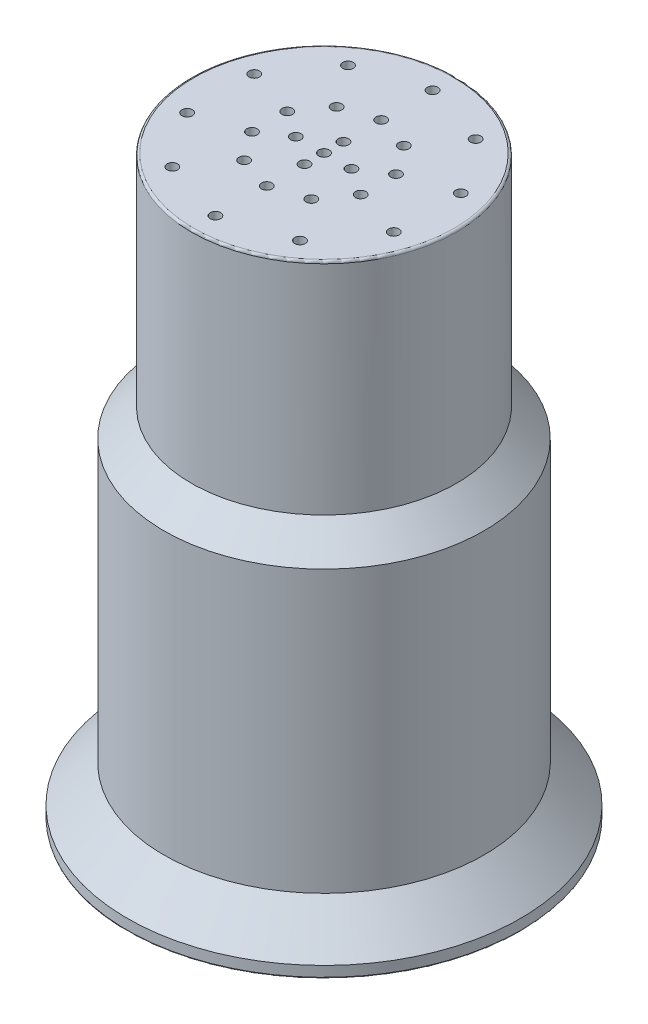
SolidWorks part; units mm, degrees
ref_plane "Front Plane" through (0, 0, 0) normal (0, 0, 1) x (1, 0, 0)
ref_plane "Top Plane" through (0, 0, 0) normal (0, 1, 0) x (1, 0, 0)
ref_plane "Right Plane" through (0, 0, 0) normal (1, 0, 0) x (0, 0, -1)
sketch "Sketch1" plane through (0, 0, 0) normal (0, 0, 1) x (1, 0, 0)
  line L0 (70, 21) -> (70, 143.8284)
  line L1 (58, 252) -> (0, 252)
  line L7 (68, 0) -> (68, 143)
  line L8 (56, 244) -> (4.0065, 244)
  line L10 (4.0065, 244) -> (0, 244)
  line L13 (86, 5) -> (86, 0)
  line L14 (86, 0) -> (68, 0)
  line L15 (0, 252) -> (0, 244)
  line L16 (70, 21) -> (86, 5)
  line L18 (58, 155.8284) -> (58, 252)
  line L20 (56, 155) -> (56, 244)
  line L25 (70, 143.8284) -> (58, 155.8284)
  line L26 (68, 143) -> (56, 155)
  line L27 (68, 143) -> (63.2647, 143) construction
  dimension "D1" = 2
  dimension "D2" = 8
  dimension "D3" = 5
  dimension "D4" = 18
  dimension "D5" = 244
  dimension "D6" = 68
  dimension "D7" = 45
  dimension "D8" = 143
  dimension "D9" = 2
  dimension "D10" = 2
  dimension "D11" = 56
  dimension "D12" = 45
revolve "Revolve1" add sketch "Sketch1" angle 360 about L15 region at (76.1172, 11.1172, 0)
sketch "Sketch2" plane through (0, 0, 0) normal (0, -1, 0) x (1, 0, 0)
  circle A0 centre (0, 0) radius 86 construction
  circle A2 centre (0, 0) radius 86 construction
  circle A4 centre (0, 0) radius 78.5 construction
  circle A5 centre (78.5, 0) radius 2.3
  dimension "D1" = 172
  dimension "D3" = 157
  dimension "D4" = 4.6
extrude "Cut-Extrude1" cut sketch "Sketch2" against normal blind 6
sketch "Sketch4" plane through (0, 252, 0) normal (0, 1, 0) x (1, 0, 0)
  circle A0 centre (0, 0) radius 25 construction
  circle A1 centre (0, 0) radius 47.5 construction
  circle A2 centre (0, 47.5) radius 2.3
  circle A3 centre (0, 25) radius 2.3
  circle A4 centre (27.9198, 38.4283) radius 2.3
  circle A5 centre (14.6946, 20.2254) radius 2.3
  circle A6 centre (45.1752, 14.6783) radius 2.3
  circle A7 centre (23.7764, 7.7254) radius 2.3
  circle A8 centre (45.1752, -14.6783) radius 2.3
  circle A9 centre (23.7764, -7.7254) radius 2.3
  circle A10 centre (27.9198, -38.4283) radius 2.3
  circle A11 centre (14.6946, -20.2254) radius 2.3
  circle A12 centre (0, -47.5) radius 2.3
  circle A13 centre (0, -25) radius 2.3
  circle A14 centre (-27.9198, -38.4283) radius 2.3
  circle A15 centre (-14.6946, -20.2254) radius 2.3
  circle A16 centre (-45.1752, -14.6783) radius 2.3
  circle A17 centre (-23.7764, -7.7254) radius 2.3
  circle A18 centre (-45.1752, 14.6783) radius 2.3
  circle A19 centre (-23.7764, 7.7254) radius 2.3
  circle A20 centre (-27.9198, 38.4283) radius 2.3
  circle A21 centre (-14.6946, 20.2254) radius 2.3
  circle A22 centre (0, 0) radius 2.3
  circle A23 centre (11.9975, 0) radius 2.3
  circle A24 centre (-12.3415, 0) radius 2.3
  circle A25 centre (0, 8.5) radius 2.3
  circle A26 centre (0, -8.5) radius 2.3
  point P47 (0, 0)
  dimension "D1" = 50
  dimension "D2" = 95
  dimension "D3" = 4.6
  dimension "D4" = 10
  dimension "D5" = 8.5
  dimension "D6" = 8.5
extrude "Cut-Extrude2" cut sketch "Sketch4" against normal blind 6
fillet "Fillet15" radius 0.5 1 edges at (-86, 0, 0)
sketch "Sketch6" plane through (0, 0, 0) normal (0, -1, 0) x (1, 0, 0)
  line L1 (-0.5, 67.5) -> (0.5, 67.5)
  line L2 (-0.5, 67.5) -> (-0.5, 64.5)
  line L3 (-0.5, 64.5) -> (0.5, 64.5)
  line L4 (0.5, 67.5) -> (0.5, 64.5)
  line L5 (-0.5, 67.5) -> (0.5, 64.5) construction
  line L6 (-0.5, 64.5) -> (0.5, 67.5) construction
  circle A0 centre (0, 0) radius 66 construction
  point P3 (0, 66)
  dimension "D3" = 132
  dimension "D1" = 3
  dimension "D2" = 1
ref_axis "Axis1" [suppressed] through (0, 280.7413, 0) along (0, -1, 0)
fillet "Fillet16" radius 1 1 edges at (-58, 252, 0)
pattern_circular "CirPattern1" count 16 over 360 about axis through (0, 0, 0) along (0, 1, 0) of "Cut-Extrude1"
fillet "Fillet17" radius 1 1 edges at (-56, 244, 0)
equation "\"ChamberRAD\"= 140 / 2"
equation "\"ChamberHeight\"= 230"
